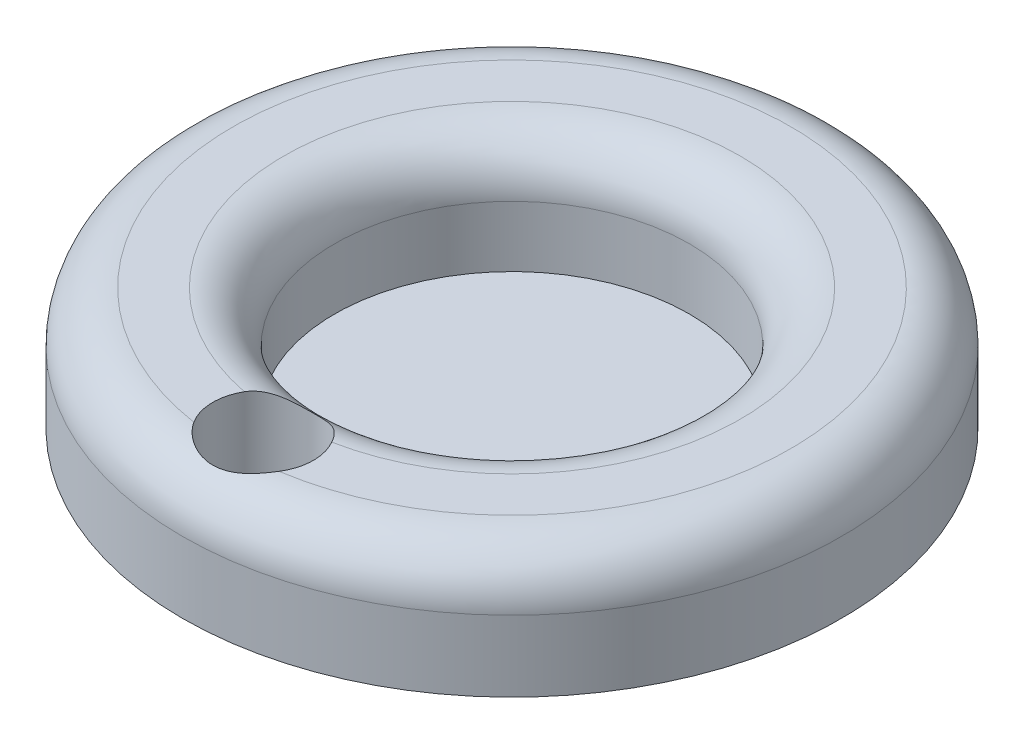
SolidWorks part; units mm, degrees
ref_plane "Alzado" through (0, 0, 0) normal (0, 0, 1) x (1, 0, 0)
ref_plane "Planta" through (0, 0, 0) normal (0, 1, 0) x (1, 0, 0)
ref_plane "Vista lateral" through (0, 0, 0) normal (1, 0, 0) x (0, 0, -1)
sketch "Croquis1" plane through (0, 0, 0) normal (0, 1, 0) x (1, 0, 0)
  line L0 (0, -32.5) -> (0, -24.54)
  circle A0 centre (0, 0) radius 32.5
  circle A1 centre (0, 0) radius 20
  circle A2 centre (0, -24.54) radius 4.96
  dimension "D1" = 65
  dimension "D2" = 40
  dimension "D4" = 9.92
  dimension "D3" = 7.96
extrude "Saliente-Extruir1" add sketch "Croquis1" along normal blind 12 contours A2 A0 A1 | A2 A1 region at (-22.331, 0, -22.331) region at (0, 0, -0.016)
sketch "Croquis2" plane through (0, 12, 0) normal (0, 1, 0) x (1, 0, 0)
  circle A0 centre (0, 0) radius 17.5
  circle A2 centre (0, 0) radius 17.5
  dimension "D1" = 35
extrude "Cortar-Extruir1" cut sketch "Croquis2" against normal blind 11 contours A0 region at (0, 12, 0)
fillet "Redondeo4" radius 5 1 edges at (0, 12, 32.5)
fillet "Redondeo5" radius 5 1 edges at (0, 12, 17.5)
